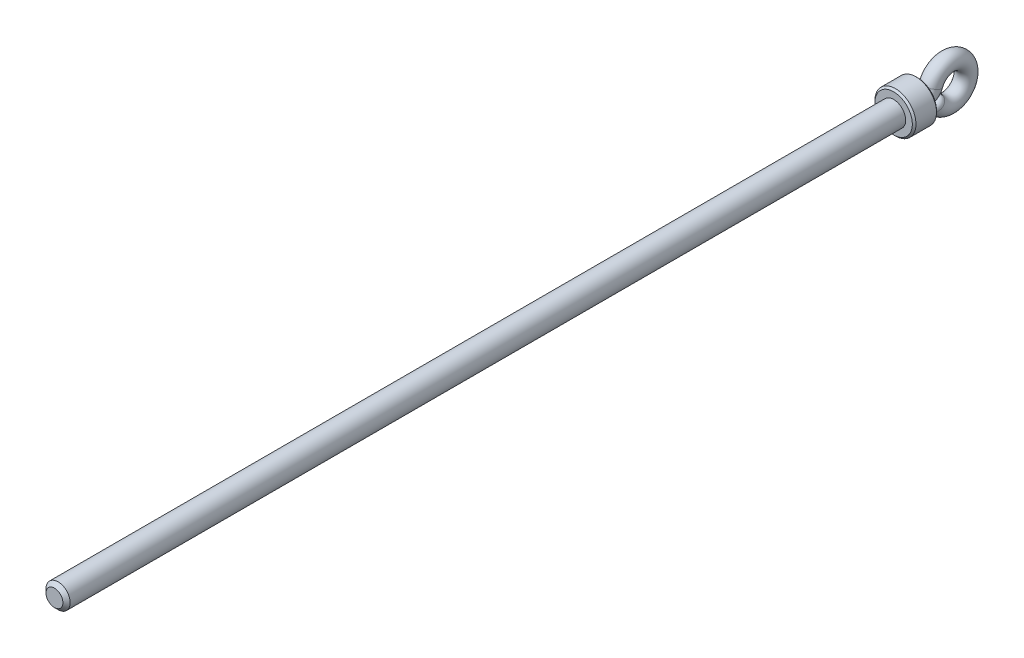
SolidWorks part; units mm, degrees
material "AISI 1020"
ref_plane "Front Plane" through (0, 0, 0) normal (0, 0, 1) x (1, 0, 0)
ref_plane "Top Plane" through (0, 0, 0) normal (0, 1, 0) x (1, 0, 0)
ref_plane "Right Plane" through (0, 0, 0) normal (1, 0, 0) x (0, 0, -1)
sketch "Sketch1" plane through (0, 0, 0) normal (0, 0, 1) x (1, 0, 0)
  circle A0 centre (0, 0) radius 10
  circle A1 centre (0, 0) radius 17
  dimension "D1" = 20
  dimension "D2" = 34
extrude "Boss-Extrude1" add sketch "Sketch1" along normal blind 695 contours A0 region at (0, 0, 0)
extrude "Boss-Extrude2" add sketch "Sketch1<3>" against normal blind 20 contours A1
sketch "Sketch1<3>" plane through (0, 0, 0) normal (0, 0, 1) x (1, 0, 0) same geometry as "Sketch1"
sketch "Sketch2" plane through (0, 0, 0) normal (1, 0, 0) x (0, 0, -1)
  line L0 (20, 0) -> (23.4361, 0)
  line L1 (20, -17) -> (20, 17) construction
  line L2 (31.0922, -5.6191) -> (45, 0) construction
  line L3 (45, 0) -> (23.4361, 0) construction
  arc A0 (23.4361, 0) -> (30.9366, 5.2174) centre (23.4361, 8) ccw
  arc A1 (30.9366, 5.2174) -> (31.0922, -5.6191) centre (45, 0) cw
  dimension "D1" = 15
  dimension "D2" = 8
  dimension "D3" = 25
  dimension "D4" = 22
sweep "Sweep1" add path "Sketch2" circular profile diameter 14 parameters "D3"=14
chamfer "Chamfer1" distance 1.5 angle 45 2 edges at (17, 0, 0) (17, 0, -20)
fillet "Fillet1" radius 2 1 edges at (0, -7, -20)
chamfer "Chamfer2" distance 3 angle 45 1 edges at (10, 0, 695)
fillet "Fillet2" radius 4 1 edges at (0, -2.9969, -37.5825)
